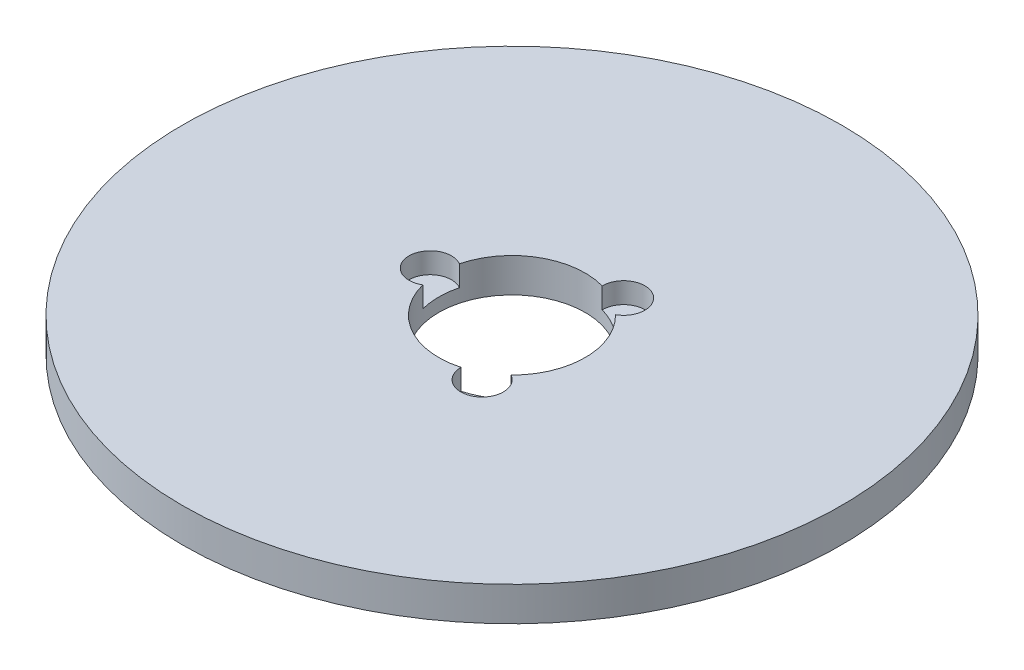
SolidWorks part; units mm, degrees
ref_plane "Front Plane" through (0, 0, 0) normal (0, 0, 1) x (1, 0, 0)
ref_plane "Top Plane" through (0, 0, 0) normal (0, 1, 0) x (1, 0, 0)
ref_plane "Right Plane" through (0, 0, 0) normal (1, 0, 0) x (0, 0, -1)
sketch "Sketch1" plane through (0, 0, 0) normal (0, 1, 0) x (1, 0, 0)
  circle A0 centre (0, 0) radius 67.5
  dimension "FLANGE_OD" = 135
extrude "Boss-Extrude1" add sketch "Sketch1" along normal blind 7
sketch "Sketch2" plane through (0, 0, 0) normal (0, 1, 0) x (1, 0, 0)
  circle A0 centre (0, 0) radius 15
  dimension "BORE_D" = 30
extrude "Cut-Extrude1" cut sketch "Sketch2" along normal through all
sketch "Sketch3" plane through (0, 7, 0) normal (0, 1, 0) x (1, 0, 0)
  circle A0 centre (0, 0) radius 16.7389 construction
  circle A1 centre (-16.7389, 0) radius 4.3514
  dimension "BOLT_D" = 8.7028
  dimension "BOLT_PCD" = 33.4778
extrude "Cut-Extrude2" cut sketch "Sketch3" against normal blind 4.2508
pattern_circular "CirPattern1" count 3 over 360 about axis through (0, 0, 0) along (0, 1, 0) of "Cut-Extrude2"
